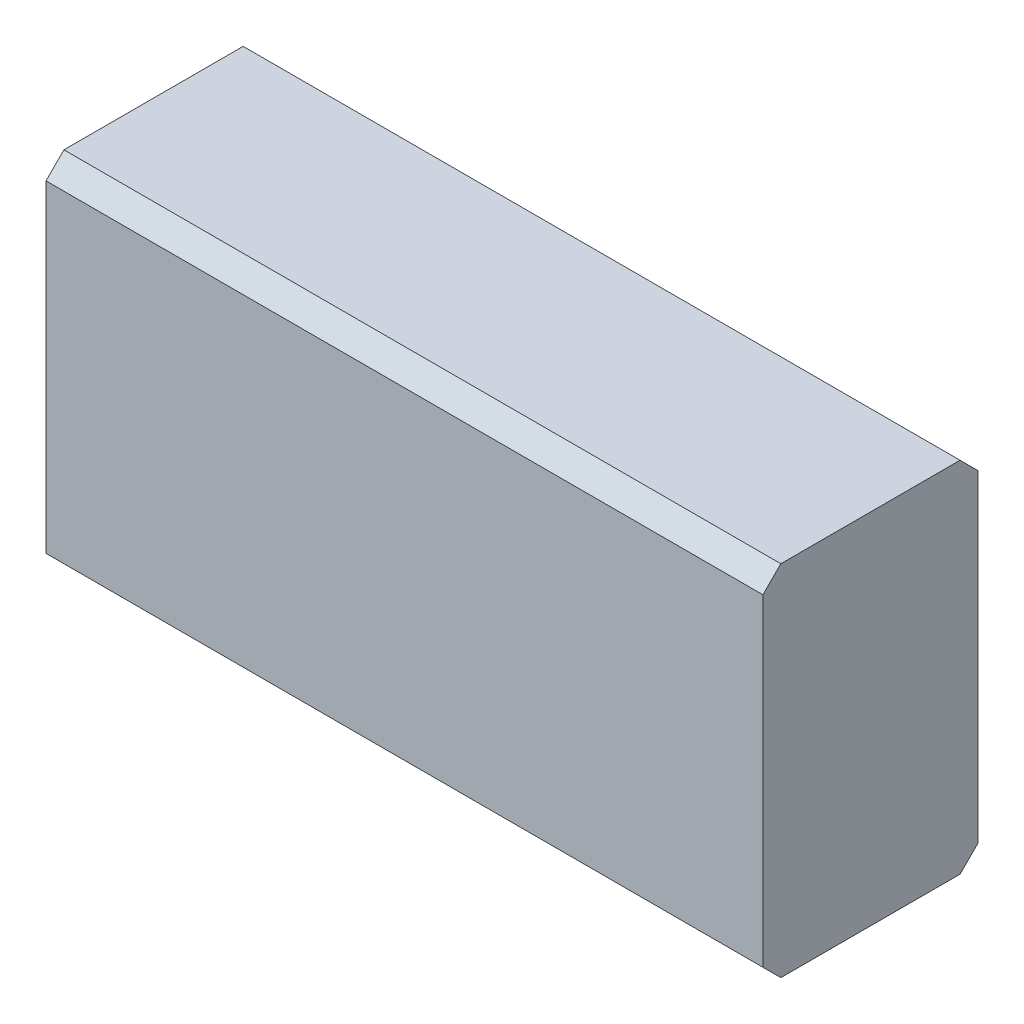
SolidWorks part; units mm, degrees
ref_plane "Front" through (0, 0, 0) normal (0, 0, 1) x (1, 0, 0)
ref_plane "Top" through (0, 0, 0) normal (0, 1, 0) x (1, 0, 0)
ref_plane "Right" through (0, 0, 0) normal (1, 0, 0) x (0, 0, -1)
sketch "Sketch1" plane through (0, 0, 0) normal (0, 0, 1) x (1, 0, 0)
  line L0 (0, 2.5) -> (-5, 2.5)
  line L1 (-5, -2.5) -> (0, -2.5)
  arc A0 (-5, 2.5) -> (-5, -2.5) centre (-5, 0) ccw
  arc A1 (0, -2.5) -> (0, 2.5) centre (0, 0) ccw
  dimension "b" = 5
  dimension "l" = 10
extrude "Extrude1" add sketch "Sketch1" along normal blind 3
sketch "Sketch2" plane through (0, 0, 0) normal (0, 0, 1) x (1, 0, 0)
  line L0 (0, 2.5) -> (-5, 2.5) construction
  line L1 (-7.5, 2.5) -> (2.5, 2.5)
  line L2 (-7.5, 2.5) -> (-7.5, -2.5)
  line L3 (-7.5, -2.5) -> (2.5, -2.5)
  line L4 (2.5, 2.5) -> (2.5, -2.5)
  line L5 (-5, -2.5) -> (0, -2.5) construction
  arc A0 (-5, 2.5) -> (-5, -2.5) centre (-5, 0) ccw construction
  arc A1 (0, -2.5) -> (0, 2.5) centre (0, 0) ccw construction
extrude "Extrude2" add sketch "Sketch2" along normal blind 3
sketch "Sketch3" plane through (0, 0, 0) normal (0, 0, 1) x (1, 0, 0)
  line L0 (-5, -2.5) -> (0, -2.5) construction
  line L1 (-5, -2.5) -> (2.5, -2.5)
  line L3 (-5, 2.5) -> (2.5, 2.5)
  line L4 (2.5, -2.5) -> (2.5, 2.5)
  arc A1 (-5, 2.5) -> (-5, -2.5) centre (-5, 0) ccw
  arc A2 (0, -2.5) -> (0, 2.5) centre (0, 0) ccw construction
  arc A3 (-5, 2.5) -> (-5, -2.5) centre (-5, 0) ccw construction
extrude "Extrude3" add sketch "Sketch3" along normal blind 3
chamfer "Chamfer1" distance 0.25 angle 45 4 edges at (-2.5, 2.5, 0) (-2.5, -2.5, 0) (-2.5, 2.5, 3) (-2.5, -2.5, 3)
equation "\"D1@Extrude2\" = \"h@Extrude1\""
equation "\"D1@Extrude3\" = \"h@Extrude1\""
